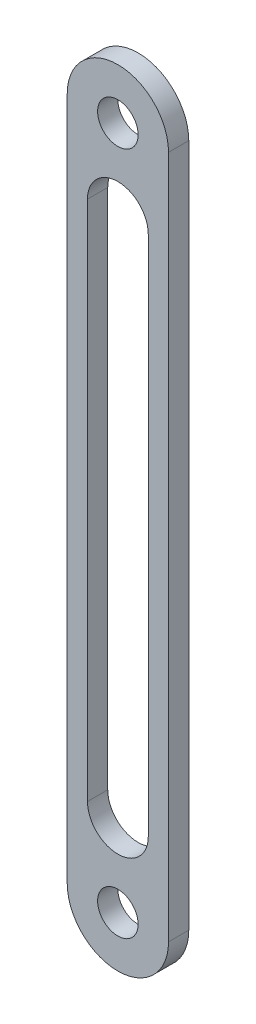
SolidWorks part; units mm, degrees
ref_plane "Alzado" through (0, 0, 0) normal (0, 0, 1) x (1, 0, 0)
ref_plane "Planta" through (0, 0, 0) normal (0, 1, 0) x (1, 0, 0)
ref_plane "Vista lateral" through (0, 0, 0) normal (1, 0, 0) x (0, 0, -1)
sketch "Croquis1" plane through (0, 0, 0) normal (0, 0, 1) x (1, 0, 0)
  line L0 (0, 67.5) -> (0, -67.5) construction
  line L1 (10, 67.5) -> (10, -67.5)
  line L2 (-10, 67.5) -> (-10, -67.5)
  line L3 (0, 51.5) -> (0, -51.5) construction
  line L4 (6, 51.5) -> (6, -51.5)
  line L5 (-6, 51.5) -> (-6, -51.5)
  arc A0 (10, 67.5) -> (-10, 67.5) centre (0, 67.5) ccw
  arc A1 (-10, -67.5) -> (10, -67.5) centre (0, -67.5) ccw
  circle A2 centre (0, 67.5) radius 4
  circle A3 centre (0, -67.5) radius 4
  arc A4 (6, 51.5) -> (-6, 51.5) centre (0, 51.5) ccw
  arc A5 (-6, -51.5) -> (6, -51.5) centre (0, -51.5) ccw
  point P2 (0, 0)
  point P14 (0, 0)
  point P19 (8.2813, 67.5)
  dimension "D1" = 8
  dimension "D2" = 20
  dimension "D3" = 135
  dimension "D4" = 4
  dimension "D5" = 16
extrude "Saliente-Extruir1" add sketch "Croquis1" along normal blind 4
